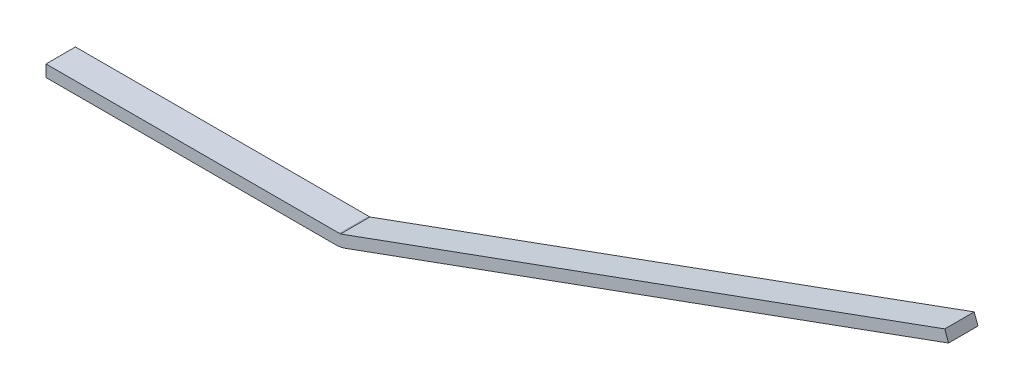
SolidWorks part; units mm, degrees
ref_plane "Płaszczyzna przednia" through (0, 0, 0) normal (0, 0, 1) x (1, 0, 0)
ref_plane "Płaszczyzna górna" through (0, 0, 0) normal (0, 1, 0) x (1, 0, 0)
ref_plane "Płaszczyzna prawa" through (0, 0, 0) normal (1, 0, 0) x (0, 0, -1)
sketch "Szkic1" plane through (0, 0, 0) normal (0, 0, 1) x (1, 0, 0)
  line L0 (1279.3124, 374.6391) -> (1497.7163, 454.1316) construction
  line L1 (-250, -10) -> (250, -10)
  line L2 (-250, -10) -> (-250, 10)
  line L3 (-250, 10) -> (250, 10)
  line L5 (-250, -10) -> (250, 10) construction
  line L6 (-250, 10) -> (250, -10) construction
  line L7 (250, -10) -> (1282.5263, 365.8089)
  line L9 (1282.5263, 365.8089) -> (1276.1078, 383.4438)
  line L10 (250, 9.9711) -> (1276.1078, 383.4438)
  line L11 (250, 9.9711) -> (250, 10)
  point P0 (0, 0)
  point P8 (240.8471, 4.4193)
  point P10 (0, 0)
  dimension "D1" = 20
  dimension "D2" = 500
  dimension "D3" = 200
extrude "Dodanie-wyciągnięcie1" add sketch "Szkic1" along normal blind 50
fillet "Zaokrąglenie1" radius 50 2 edges at (250, 10, 25) (250, -10, 25)
